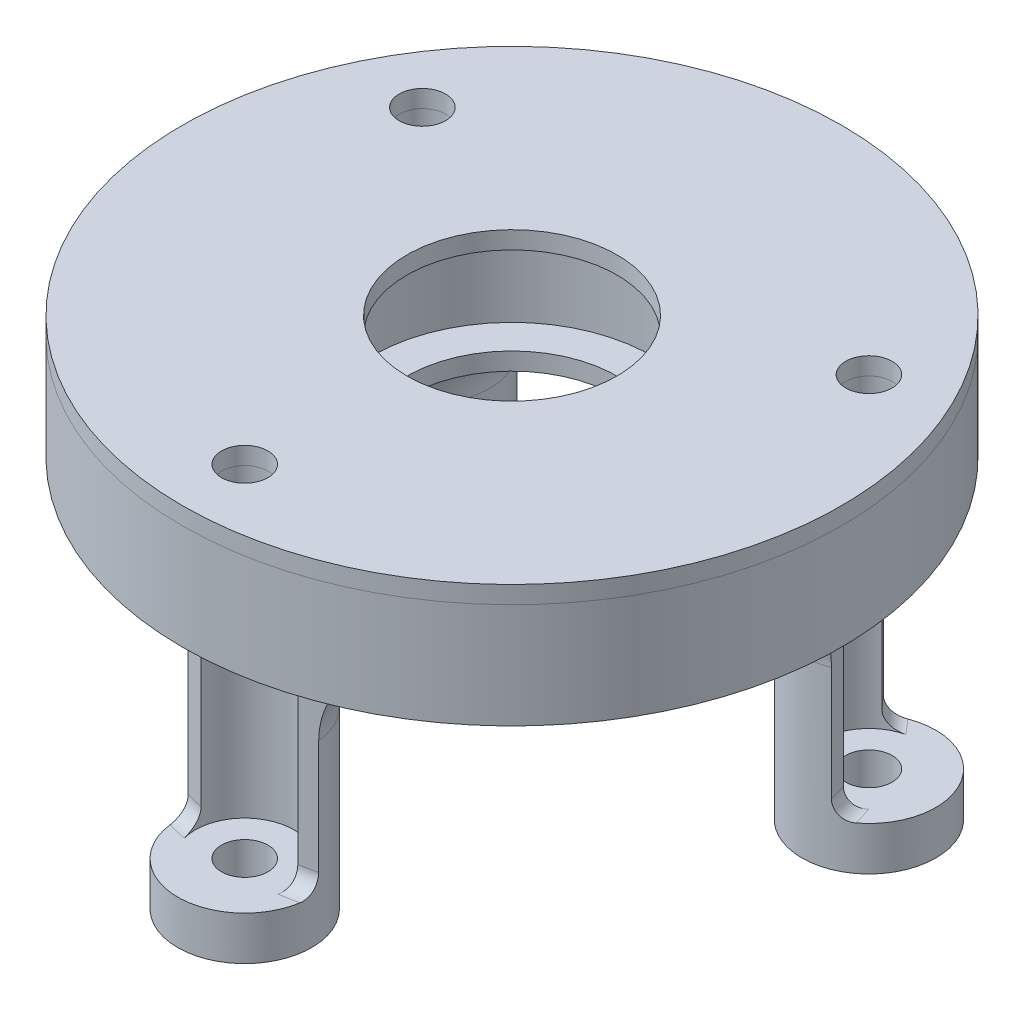
SolidWorks part; units mm, degrees
ref_plane "Front Plane" through (0, 0, 0) normal (0, 0, 1) x (1, 0, 0)
ref_plane "Top Plane" through (0, 0, 0) normal (0, 1, 0) x (1, 0, 0)
ref_plane "Right Plane" through (0, 0, 0) normal (1, 0, 0) x (0, 0, -1)
sketch "Sketch1" plane through (0, 0, 0) normal (0, 1, 0) x (1, 0, 0)
  line L0 (0, 0) -> (26.247, 14.5292) construction
  line L1 (0, 0) -> (-25.7061, 15.466) construction
  line L2 (0, 0) -> (-0.5409, -29.9951) construction
  circle A0 centre (0, 0) radius 30
  circle A1 centre (-25.7061, 15.466) radius 2.65
  circle A2 centre (26.247, 14.5292) radius 2.65
  circle A3 centre (-0.5409, -29.9951) radius 2.65
  circle A4 centre (-25.7061, 15.466) radius 7.65
  circle A5 centre (26.247, 14.5292) radius 7.65
  circle A6 centre (-0.5409, -29.9951) radius 7.65
  circle A7 centre (-25.7061, 15.466) radius 5.65
  circle A8 centre (26.247, 14.5292) radius 5.65
  circle A9 centre (-0.5409, -29.9951) radius 5.65
  dimension "D1" = 60
  dimension "D4" = 5.3
  dimension "D2" = 120
  dimension "D3" = 120
  dimension "D5" = 5
  dimension "D6" = 2
extrude "Boss-Extrude1" add sketch "Sketch1" along normal blind 5 contours A0 A9 A3 | A0 A9 A3 | A9 A0 A6 | A9 A0 A6 | A0 A7 A1 | A7 A0 A4 | A0 A7 A1 | A7 A0 A4 | A8 A0 A5 | A0 A8 A2 | A0 A8 A2 | A8 A0 A5 region at (19.7057, 0, -10.9082) region at (28.9869, 0, -8.4426) region at (6.9216, 0, 29.585) region at (6.0472, 0, 29.2126) region at (23.7259, 0, -13.1336) region at (28.1318, 0, -10.817) region at (4.9758, 0, 29.7846) region at (-0.4889, 0, 27.114) region at (-18.9761, 0, -18.7224) region at (-21.8054, 0, -20.8825) region at (-23.237, 0, -13.9804) region at (-23.434, 0, -18.9547)
extrude "Boss-Extrude2" add sketch "Sketch1<3>" along normal blind 30 contours A7 A0 A4 | A8 A0 A5 | A9 A0 A6 region at (19.7057, 0, -10.9082) region at (6.0472, 0, 29.2126) region at (-18.9761, 0, -18.7224)
sketch "Sketch1<3>" plane through (0, 0, 0) normal (0, 1, 0) x (1, 0, 0) same geometry as "Sketch1"
ref_plane "Plane1" through (0, 30, 0) normal (0, 1, 0) x (1, 0, 0)
sketch "Sketch2" plane through (0, 30, 0) normal (0, 1, 0) x (1, 0, 0)
  circle A0 centre (0, 0) radius 37.65
  circle A1 centre (0, 0) radius 16
  circle A2 centre (0, 0) radius 12
  dimension "D1" = 32
  dimension "D2" = 4
extrude "Boss-Extrude3" add sketch "Sketch2" along normal blind 12 contours A0 A1 region at (-36.5851, 30, 0)
extrude "Cut-Extrude1" cut sketch "Sketch1<4>" along normal up to surface (42 mm away) contours A0 A2 | A0 A2 | A0 A3 | A0 A3 | A0 A1 | A0 A1 region at (25.2448, 0, -13.9744) region at (27.2123, 0, -15.0635) region at (-0.5608, 0, 31.0983) region at (-0.5202, 0, 28.8498) region at (-24.7246, 0, -14.8754) region at (-26.6515, 0, -16.0348) up to face at (0, 42, 16)
sketch "Sketch1<4>" plane through (0, 0, 0) normal (0, 1, 0) x (1, 0, 0) same geometry as "Sketch1"
extrude "Boss-Extrude4" add sketch "Sketch2<3>" along normal blind 2 contours A1 A2 region at (-15.5475, 30, 0)
sketch "Sketch2<3>" plane through (0, 30, 0) normal (0, 1, 0) x (1, 0, 0) same geometry as "Sketch2"
ref_plane "Plane2" through (0, 42, 0) normal (0, 1, 0) x (1, 0, 0)
sketch "Sketch3" plane through (0, 42, 0) normal (0, 1, 0) x (1, 0, 0)
  circle A0 centre (0, 0) radius 12 construction
  circle A1 centre (0, 0) radius 37.65 construction
  circle A2 centre (0, 0) radius 12
  circle A3 centre (0, 0) radius 37.65
  circle A4 centre (-0.5409, -29.9951) radius 2.65 construction
  circle A5 centre (26.247, 14.5292) radius 2.65 construction
  circle A6 centre (-25.7061, 15.466) radius 2.65 construction
  circle A7 centre (-0.5409, -29.9951) radius 2.65
  circle A8 centre (26.247, 14.5292) radius 2.65
  circle A9 centre (-25.7061, 15.466) radius 2.65
extrude "Boss-Extrude5" add sketch "Sketch3" along normal blind 2 separate body
fillet "Fillet1" radius 10 3 edges at (19.554, 30, -10.8242) (-0.4029, 30, 22.3464) (-19.1511, 30, -11.5221)
fillet "Fillet2" radius 2 6 edges at (22.4007, 5, -19.9551) (28.8032, 5, -8.3891) (-28.482, 5, -9.422) (-21.6667, 5, -20.7498) (6.0813, 5, 29.3772) (-7.1364, 5, 29.1388)
